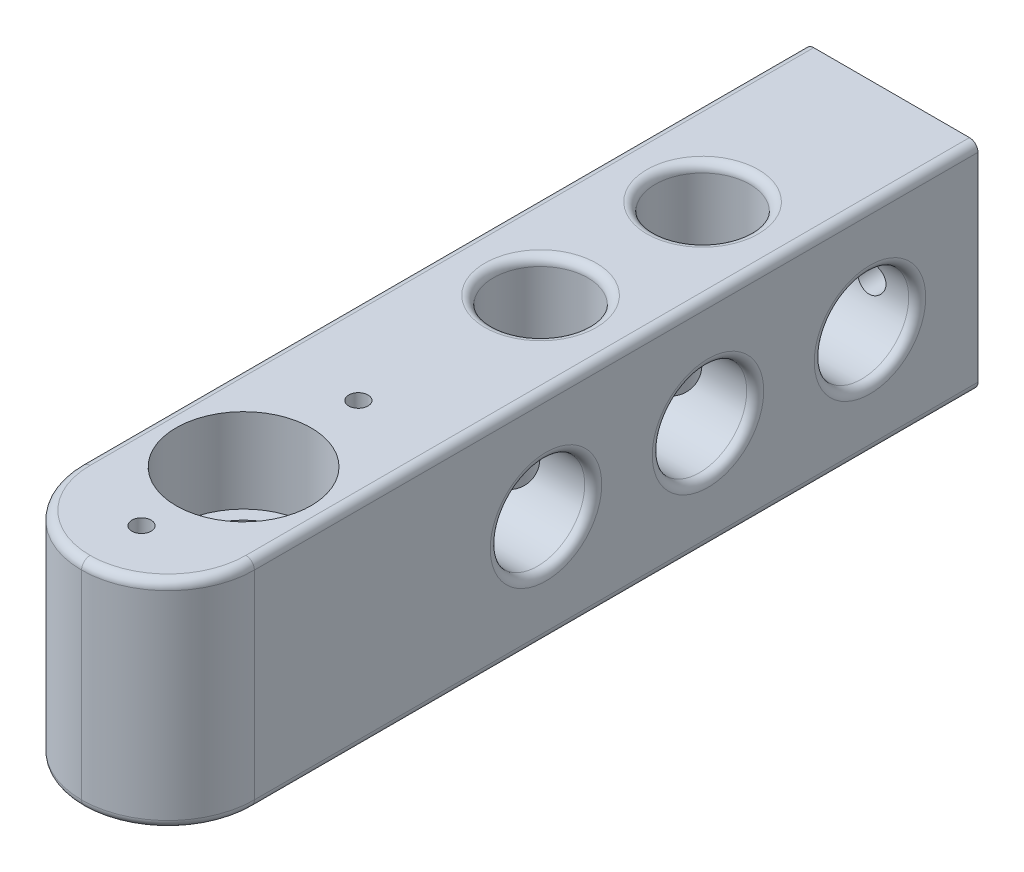
SolidWorks part; units mm, degrees
material "6061 Alloy"
ref_plane "Front Plane" through (0, 0, 0) normal (0, 0, 1) x (1, 0, 0)
ref_plane "Top Plane" through (0, 0, 0) normal (0, 1, 0) x (1, 0, 0)
ref_plane "Right Plane" through (0, 0, 0) normal (1, 0, 0) x (0, 0, -1)
sketch "Sketch2" plane through (0, 0, 0) normal (0, 0, 1) x (1, 0, 0)
  line L0 (10.16, 12.6998) -> (-10.16, 12.6998)
  line L1 (10.16, -12.6998) -> (-10.16, -12.6998)
  line L2 (10.16, -12.6998) -> (-10.16, 12.6998) construction
  line L3 (-10.16, -12.6998) -> (10.16, 12.6998) construction
  line L7 (-10.16, 12.6998) -> (-10.16, -12.6998)
  line L8 (10.16, 12.6998) -> (10.16, -12.6998)
  dimension "D1" = 20.32
  dimension "D2" = 25.3997
extrude "Body" add sketch "Sketch2" along normal blind 95.25 contours L8 L7 region at (0, 0, 0)
sketch "Sketch3" plane through (0, 12.6998, 0) normal (0, 1, 0) x (1, 0, 0)
  line L0 (10.16, -95.25) -> (-10.16, -95.25) construction
  line L1 (0, 0) -> (0, -95.25) construction
  line L2 (10.16, 0) -> (-10.16, 0) construction
  circle A0 centre (0, -76.2) radius 5
  circle A1 centre (0, -76.2) radius 6.35
  dimension "D2" = 10
  dimension "D3" = 12.7
  dimension "D1" = 19.05
extrude "Yaw Axle Opening" cut sketch "Sketch3" against normal through all contours A0 | L1 A0 region at (2.1221, 12.6998, 76.2) region at (-2.1221, 12.6998, 76.2)
extrude "Top Yaw Bearing" cut sketch "Sketch3<3>" against normal blind 3.9675 from offset 9.9225 offset against normal yes
sketch "Sketch3<3>" plane through (0, 12.6998, 0) normal (0, 1, 0) x (1, 0, 0) same geometry as "Sketch3"
extrude "Lower Yaw Bearing" cut sketch "Sketch3<4>" along normal blind 3.9675 from offset 25.4 offset against normal yes
sketch "Sketch3<4>" plane through (0, 12.6998, 0) normal (0, 1, 0) x (1, 0, 0) same geometry as "Sketch3"
sketch "Sketch5" plane through (0, 12.6998, 0) normal (0, 1, 0) x (1, 0, 0)
  circle A0 centre (0, -76.2) radius 7.9375
  dimension "D1" = 15.875
extrude "Yaw Axle Cap Recess" cut sketch "Sketch5" against normal blind 9.9225
hole_wizard "#4-40 Tapped Hole1" positions "3DSketch2" profile "Sketch6" tap size "#4-40" standard "ANSI Inch"
sketch3d "3DSketch2"
  line L3 (0, 12.6998, 76.2) -> (0, 12.6998, 95.25) construction
  line L4 (0, -1.1902, 76.2) -> (0, 2.7773, 76.2) construction
  line L18 (10.16, 12.6998, 88.2) -> (-10.16, 12.6998, 88.2) construction
  line L19 (0, 12.6998, 76.2) -> (0, 12.6998, 0) construction
  line L22 (10.16, 12.6998, 62.7) -> (-10.16, 12.6998, 62.7) construction
  line L25 (10.16, 12.6998, 0) -> (-10.16, 12.6998, 0) construction
  line L26 (-10.16, 12.6998, 95.25) -> (-10.16, 12.6998, 0) construction
  line L28 (10.16, 12.6998, 95.25) -> (10.16, 12.6998, 0) construction
  line L29 (10.16, 12.6998, 95.25) -> (-10.16, 12.6998, 95.25) construction
  point P0 (0, 12.6998, 62.7)
  point P2 (0, 12.6998, 88.2)
  dimension "D1" = 12
  dimension "D2" = 13.5
sketch "Sketch6" plane through (0, 12.6998, 62.7) normal (1, 0, 0) x (0, 0, 1)
  line L0 (0, 0) -> (0, 5.7592)
  line L1 (0, 5.7592) -> (1.1303, 5.08)
  line L2 (1.1303, 5.08) -> (1.1303, 0)
  line L5 (1.1303, 0) -> (0, 0)
  line L10 (0, 5.7592) -> (-1.1303, 5.08) construction
  line L11 (0, -6.35) -> (0, 107.95) construction
  dimension "Tap Drill Dia." = 2.2606
  dimension "Tap Drill Depth" = 5.08
  dimension "Drill Angle" = 118
cosmetic thread "Hole Thread8" parameters "D1"=5.08, "D2"=2.8448
cosmetic thread "Hole Thread9" parameters "D1"=5.08, "D2"=2.8448
hole_wizard "#8-32 Tapped Hole1" positions "3DSketch3" profile "Sketch7" tap size "#8-32" standard "Ansi Inch"
sketch3d "3DSketch3"
  line L0 (10.16, 0, 0) -> (-10.16, 0, 0) construction
  line L1 (10.16, 12.6998, 0) -> (10.16, -12.6998, 0) construction
  line L2 (-10.16, 12.6998, 0) -> (-10.16, -12.6998, 0) construction
  line L3 (0, 12.6998, 0) -> (0, -12.6998, 0) construction
  line L6 (4.7625, 12.6998, 0) -> (4.7625, -12.6998, 0) construction
  line L7 (-4.7625, 12.6998, 0) -> (-4.7625, -12.6998, 0) construction
  line L8 (10.16, 12.6998, 0) -> (-10.16, 12.6998, 0) construction
  line L9 (10.16, -12.6998, 0) -> (-10.16, -12.6998, 0) construction
  point P0 (4.7625, 0, 0)
  point P2 (-4.7625, 0, 0)
  dimension "D1" = 4.7625
  dimension "D2" = 4.7625
sketch "Sketch7" plane through (4.7625, 0, 0) normal (1, 0, 0) x (0, 1, 0)
  line L0 (0, 0) -> (0, 11.7464)
  line L1 (0, 11.7464) -> (1.7272, 10.7086)
  line L2 (1.7272, 10.7086) -> (1.7272, 0)
  line L5 (1.7272, 0) -> (0, 0)
  line L10 (0, 11.7464) -> (-1.7272, 10.7086) construction
  line L11 (0, -6.35) -> (0, 107.95) construction
  dimension "Tap Drill Dia." = 3.4544
  dimension "Tap Drill Depth" = 10.7086
  dimension "Drill Angle" = 118
cosmetic thread "Hole Thread5" parameters "D1"=7.419, "D2"=4.1656
cosmetic thread "Hole Thread6" parameters "D1"=7.419, "D2"=4.1656
hole_wizard "#6-32 Tapped Hole2" positions "Sketch9" profile "Sketch8" tap size "#6-32" standard "ANSI Inch"
sketch "Sketch9" plane through (-5.9383, -12.6998, -21.9181) normal (0, -1, 0) x (1, 0, 0)
  line L0 (5.9383, 21.9181) -> (5.9383, 72.7181) construction
  line L1 (16.0983, 21.9181) -> (-4.2217, 21.9181) construction
  point P0 (5.9383, 72.7181)
  dimension "D1" = 50.8
sketch "Sketch8" plane through (0, -12.6998, 50.8) normal (1, 0, 0) x (0, 0, -1)
  line L0 (0, 0) -> (0, 5.8927)
  line L1 (0, 5.8927) -> (1.3525, 5.08)
  line L2 (1.3525, 5.08) -> (1.3525, 0)
  line L5 (1.3525, 0) -> (0, 0)
  line L10 (0, 5.8927) -> (-1.3526, 5.08) construction
  line L11 (0, -6.35) -> (0, 107.95) construction
  dimension "Tap Drill Dia." = 2.7051
  dimension "Tap Drill Depth" = 5.08
  dimension "Drill Angle" = 118
cosmetic thread "Hole Thread10" parameters "D1"=5.08, "D2"=3.5052
hole_wizard "7/16 (0.4375) Diameter Hole1" positions "3DSketch4" profile "Sketch12" hole size "7/16" standard "Ansi Inch" end condition through all
sketch3d "3DSketch4"
  line L0 (-10.16, 0, 0) -> (-10.16, 0, 95.25) construction
  line L1 (-10.16, 12.6998, 0) -> (-10.16, -12.6998, 0) construction
  line L4 (0, 12.6998, 0) -> (0, 12.6998, 95.25) construction
  line L5 (10.16, 12.6998, 0) -> (-10.16, 12.6998, 0) construction
  line L8 (-10.16, 12.6998, 95.25) -> (-10.16, -12.6998, 95.25) construction
  line L10 (-10.16, 12.6998, 0) -> (-10.16, -12.6998, 0) construction
  line L11 (10.16, 12.6998, 95.25) -> (-10.16, 12.6998, 95.25) construction
  point P0 (-10.16, 0, 12.7)
  point P2 (-10.16, 0, 31.75)
  point P4 (-10.16, 0, 50.8)
  point P26 (0, 12.6998, 22.225)
  point P28 (0, 12.6998, 41.275)
  dimension "D1" = 12.7
  dimension "D2" = 19.05
  dimension "D3" = 19.05
  dimension "D5" = 22.225
  dimension "D6" = 19.05
sketch "Sketch12" plane through (-10.16, 0, 12.7) normal (0, 1, 0) x (0, 0, 1)
  line L0 (0, 0) -> (0, 20.32)
  line L1 (0, 20.32) -> (5.5562, 20.32)
  line L2 (5.5562, 20.32) -> (5.5562, 0)
  line L5 (5.5562, 0) -> (0, 0)
  line L11 (0, -6.35) -> (0, 107.95) construction
  dimension "Thru Hole Dia." = 11.1125
  dimension "Thru Hole Depth" = 20.32
fillet "Fillet1" radius 10.16 2 edges at (-10.16, 0, 95.25) (10.16, 0, 95.25)
fillet "Fillet3" radius 1 18 edges at (-7.1842, -12.6998, 92.2742) (7.1842, -12.6998, 92.2742) (-7.1842, 12.6998, 92.2742) (7.1842, 12.6998, 92.2742) (-10.16, -12.6998, 42.545) (10.16, -12.6998, 42.545) (-10.16, 12.6998, 42.545) (10.16, 12.6998, 42.545) (0, -12.6998, 27.7812) (0, -12.6998, 46.8312) (-10.16, 0, 18.2562) (-10.16, 0, 37.3062) (-10.16, 0, 56.3562) (0, 12.6998, 46.8312) (0, 12.6998, 27.7812) (10.16, 0, 18.2562) (10.16, 0, 37.3062) (10.16, 0, 56.3562)
